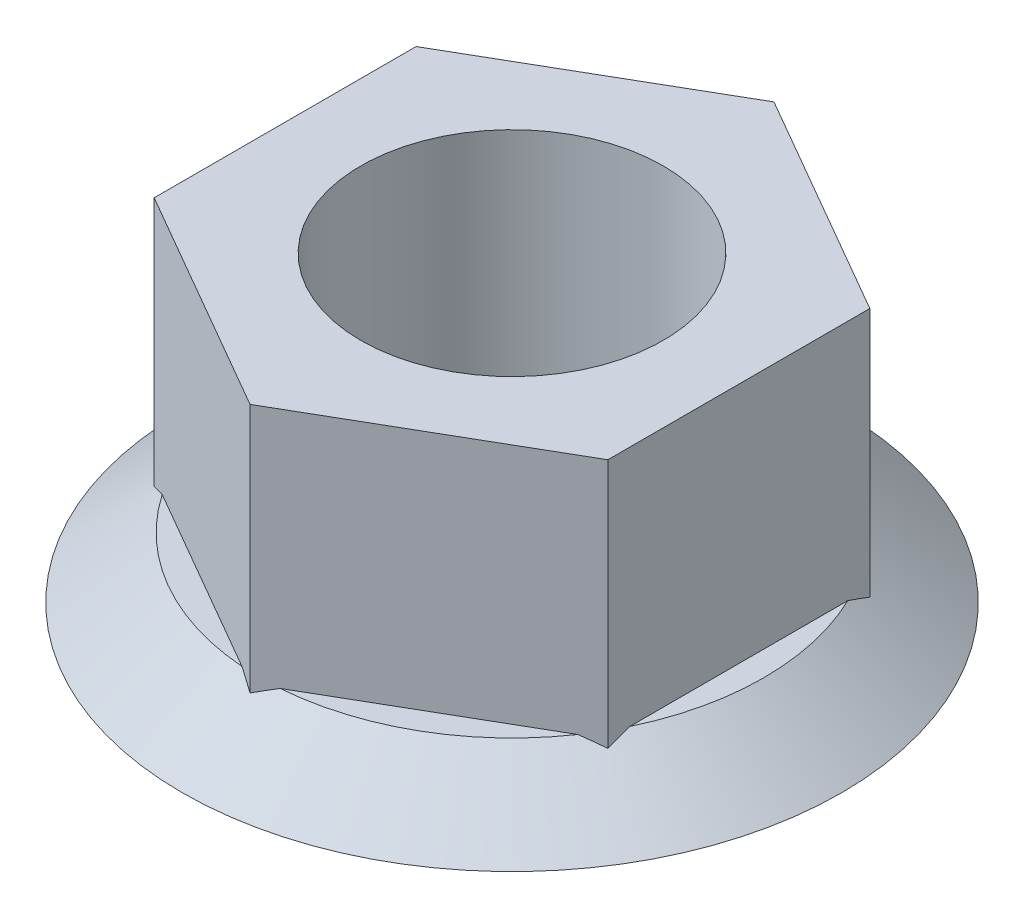
SolidWorks part; units mm, degrees
ref_plane "Płaszczyzna przednia" through (0, 0, 0) normal (0, 0, 1) x (1, 0, 0)
ref_plane "Płaszczyzna górna" through (0, 0, 0) normal (0, 1, 0) x (1, 0, 0)
ref_plane "Płaszczyzna prawa" through (0, 0, 0) normal (1, 0, 0) x (0, 0, -1)
sketch "Szkic1" plane through (0, 0, 0) normal (0, 0, 1) x (1, 0, 0)
  line L0 (5, 0) -> (5, 2)
  line L1 (5, 2) -> (8.32, 2)
  line L2 (8.32, 2) -> (10.9, 0)
  line L3 (10.9, 0) -> (5, 0)
  line L4 (0, 0) -> (0, 48.4102) construction
  point P8 (5, 0.5047)
  dimension "D1" = 5
  dimension "D2" = 10.9
  dimension "D3" = 2
  dimension "D4" = 8.32
revolve "Obrót1" add sketch "Szkic1" angle 360 about L4
sketch "Szkic2" plane through (0, 2, 0) normal (0, 1, 0) x (1, 0, 0)
  line L1 (0, 8.6603) -> (-7.5, 4.3301)
  line L2 (-7.5, 4.3301) -> (-7.5, -4.3301)
  line L3 (-7.5, -4.3301) -> (0, -8.6603)
  line L4 (0, -8.6603) -> (7.5, -4.3301)
  line L5 (7.5, -4.3301) -> (7.5, 4.3301)
  line L6 (7.5, 4.3301) -> (0, 8.6603)
  circle A0 centre (0, 0) radius 7.5 construction
  circle A1 centre (0, 0) radius 5
  dimension "D1" = 15
extrude "Dodanie-wyciągnięcie1" add sketch "Szkic2" along normal blind 10 from surface starting at face at (0, 0, -10.9)
